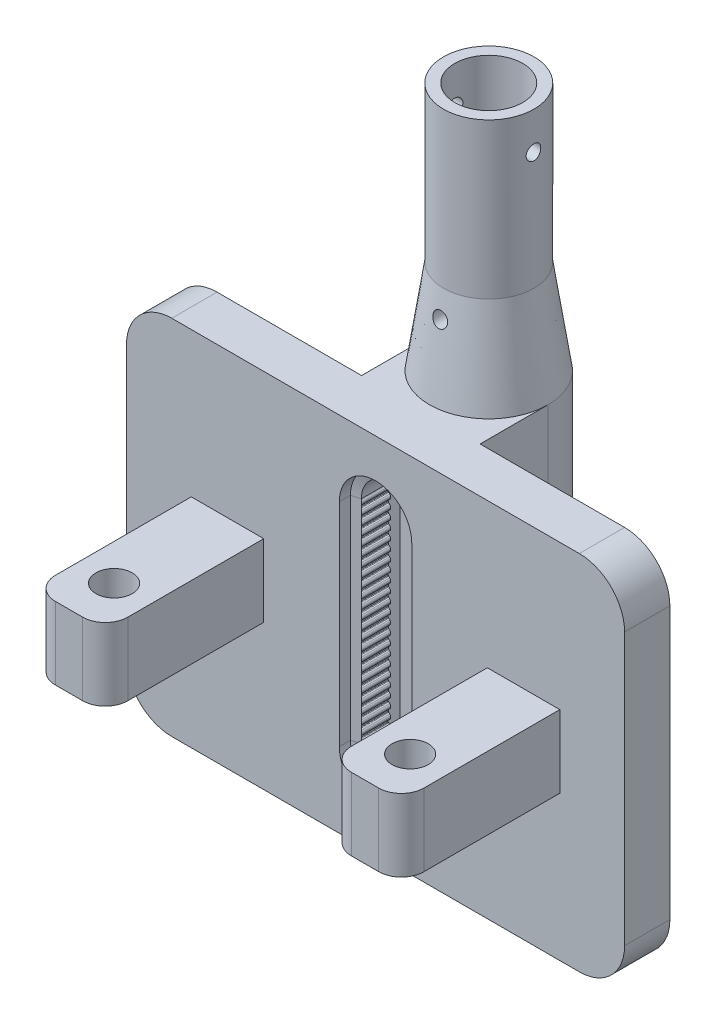
SolidWorks part; units mm, degrees
ref_plane "Piano frontale" through (0, 0, 0) normal (0, 0, 1) x (1, 0, 0)
ref_plane "Piano superiore" through (0, 0, 0) normal (0, 1, 0) x (1, 0, 0)
ref_plane "Piano destro" through (0, 0, 0) normal (1, 0, 0) x (0, 0, -1)
sketch "Schizzo1" plane through (0, 0, 0) normal (0, 0, 1) x (1, 0, 0)
  line L1 (-55, 40) -> (55, 40)
  line L2 (-55, 40) -> (-55, -40)
  line L3 (-55, -40) -> (55, -40)
  line L4 (55, 40) -> (55, -40)
  line L5 (-55, 40) -> (55, -40) construction
  line L6 (-55, -40) -> (55, 40) construction
  point P0 (0, 0)
  dimension "D1" = 80
  dimension "D2" = 110
extrude "Estrusione-Estrusione1" add sketch "Schizzo1" along normal blind 10
fillet "Raccordo1" radius 10 4 edges at (-55, -40, 5) (55, -40, 5) (55, 40, 5) (-55, 40, 5)
sketch "Schizzo2" plane through (0, 0, 10) normal (0, 0, 1) x (1, 0, 0)
  line L1 (-6.11, 27.5) -> (6.11, 27.5)
  line L2 (-6.11, 27.5) -> (-6.11, -27.5)
  line L3 (-6.11, -27.5) -> (6.11, -27.5)
  line L4 (6.11, 27.5) -> (6.11, -27.5)
  line L5 (-6.11, 27.5) -> (6.11, -27.5) construction
  line L6 (-6.11, -27.5) -> (6.11, 27.5) construction
  point P0 (0, 0)
  dimension "D1" = 55
  dimension "D2" = 12.22
extrude "Estrusione-Estrusione2" add sketch "Schizzo2" against normal blind 5 contours L1 L4 L3 L2
sketch "Schizzo6" plane through (0, 0, 10) normal (0, 0, 1) x (1, 0, 0)
  line L0 (0, 0) -> (49.9303, 0) construction
  line L2 (-6.11, 21.3859) -> (-6.11, -21.3859)
  line L4 (6.11, 21.3859) -> (6.11, -21.3859)
  line L5 (-6.11, 27.5) -> (6.11, -27.5) construction
  line L6 (-6.11, -27.5) -> (6.11, 27.5) construction
  arc A1 (6.11, -21.3859) -> (-6.11, -21.3859) centre (0, -21.3859) cw
  arc A2 (6.11, 21.3859) -> (-6.11, 21.3859) centre (0, 21.3859) ccw
  point P0 (0, 0)
  dimension "D1" = 12.22
  dimension "D2" = 55
extrude "Taglio-Estrusione6" cut sketch "Schizzo6" against normal blind 20
sketch "Schizzo9" plane through (0, 0, 0) normal (0, 0, -1) x (-1, 0, 0)
  line L0 (0, 0) -> (-26.4048, 0) construction
  line L1 (6.11, 23.4312) -> (6.11, -23.4312)
  line L2 (-6.11, 23.4312) -> (-6.11, -23.4312)
  arc A4 (6.11, 23.4312) -> (-6.11, 23.4312) centre (0, 23.4312) ccw
  arc A5 (-6.11, -23.4312) -> (6.11, -23.4312) centre (0, -23.4312) ccw
  point P0 (0, 0)
extrude "Taglio-Estrusione8" cut sketch "Schizzo9" against normal blind 53 contours A5 L1 A4 L2
ref_plane "Piano1" through (0, 95, 0) normal (0, 1, 0) x (1, 0, 0)
sketch "Schizzo14" plane through (0, 95, 0) normal (0, 1, 0) x (1, 0, 0)
  circle A1 centre (0, 15) radius 10
  dimension "D2" = 20
extrude "Estrusione-Estrusione5" add sketch "Schizzo14" against normal blind 135 separate body
ref_plane "Piano2" through (0, 0, 5) normal (0, 0, 1) x (1, 0, 0)
ref_plane "Piano3" through (0, -40, 0) normal (0, 1, 0) x (1, 0, 0)
sketch "Schizzo20" plane through (0, -40, 0) normal (0, 1, 0) x (1, 0, 0)
  line L0 (-13.0862, 15) -> (-13.0862, 0)
  line L1 (-45, 0) -> (45, 0) construction
  line L2 (-13.0862, 0) -> (13.0862, 0)
  line L3 (13.0862, 0) -> (13.0862, 15)
  arc A0 (13.0862, 15) -> (-13.0862, 15) centre (0, 15) ccw
chamfer "Smusso1" distance 2 angle 15 4 edges at (-6.11, 0, 0) (0, 29.5412, 0) (6.11, 0, 0) (0, -29.5412, 0) first distance on face at (0, 0, 0)
ref_plane "Piano4" through (0, 0, 7) normal (0, 0, 1) x (1, 0, 0)
sketch "Schizzo22" plane through (0, 0, 7) normal (0, 0, 1) x (1, 0, 0)
  line L0 (0, 0) -> (47.566, 0) construction
  line L1 (-8, 23.4312) -> (-8, -23.4312)
  line L2 (8, 23.4312) -> (8, -23.4312)
  arc A0 (8, 23.4312) -> (-8, 23.4312) centre (0, 23.4312) ccw
  arc A1 (8, -23.4312) -> (-8, -23.4312) centre (0, -23.4312) cw
extrude "Taglio-Estrusione12" cut sketch "Schizzo22" along normal blind 80 contours A0 L1 A1 L2
chamfer "Smusso2" distance 2 angle 15 4 edges at (0, -31.4312, 7) (-8, 0, 7) (0, 31.4312, 7) (8, 0, 7) first distance on face at (0, 0, 7)
extrude "Estrusione-Estrusione9" add sketch "Schizzo20" along normal blind 8 contours L0 L2 L3 A0
sketch "Schizzo23" plane through (0, -32, 0) normal (0, 1, 0) x (1, 0, 0)
  line L0 (-13.0862, 15) -> (-13.0862, 0)
  line L1 (-13.0862, 0) -> (-8.5862, 0)
  line L2 (-13.0862, 0) -> (13.0862, 0) construction
  line L3 (-8.5862, 0) -> (-6.5862, 2)
  line L4 (-6.5862, 2) -> (6.5862, 2)
  line L5 (6.5862, 2) -> (8.5862, 0)
  line L6 (-13.0862, 0) -> (13.0862, 0) construction
  line L7 (8.5862, 0) -> (13.0862, 0)
  line L8 (13.0862, 0) -> (13.0862, 15)
  arc A0 (13.0862, 15) -> (-13.0862, 15) centre (0, 15) ccw
  dimension "D1" = 4.5
  dimension "D2" = 45
  dimension "D3" = 4.5
  dimension "D4" = 2
extrude "Estrusione-Estrusione10" add sketch "Schizzo23" along normal blind 64
sketch "Schizzo24" plane through (0, 32, 0) normal (0, 1, 0) x (1, 0, 0)
  line L0 (-13.0862, 15) -> (-13.0862, 0)
  line L1 (-13.0862, 0) -> (13.0862, 0)
  line L2 (13.0862, 0) -> (13.0862, 15)
  arc A0 (13.0862, 15) -> (-13.0862, 15) centre (0, 15) ccw
extrude "Estrusione-Estrusione11" add sketch "Schizzo24" along normal blind 8
sketch "Schizzo25" plane through (0, 0, 0) normal (1, 0, 0) x (0, 0, -1)
  line L0 (15, 40) -> (15, 81.458) construction
  line L1 (15, 40) -> (28.0862, 40)
  line L2 (28.0862, 40) -> (25, 60.729)
  line L3 (25, 40) -> (25, 95) construction
  line L4 (25, 60.729) -> (15, 60.729)
  line L5 (15, 60.729) -> (15, 40)
revolve "Rivoluzione6" add sketch "Schizzo25" angle 360 about L0
sketch "Schizzo26" plane through (0, 0, 7) normal (0, 0, 1) x (1, 0, 0)
  line L0 (1.3785, -23.4315) -> (-1.3779, -23.431)
  line L1 (-6.8597, 21.1652) -> (-6.8597, 21.6893)
  line L2 (-6.8571, 15.416) -> (-6.8578, 15.1539)
  line L3 (-6.8575, 23.4312) -> (-6.8581, 23.1691)
  line L4 (-6.8571, 7.4009) -> (-6.8578, 7.1388)
  line L5 (-6.1096, 8.4039) -> (-6.1096, 8.4032) construction
  line L6 (1.3785, 23.4309) -> (-6.8575, 23.4312)
  line L7 (-6.8574, 19.4235) -> (-6.858, 19.6856)
  line L8 (-6.1096, 22.4287) -> (-6.1096, 22.4291) construction
  line L9 (-6.8571, -8.6292) -> (-6.8578, -8.8913)
  line L10 (-6.8574, 11.4084) -> (-6.858, 11.6705)
  line L11 (-6.1096, 22.4291) -> (-6.1096, 22.4287)
  line L12 (-6.1096, 22.4287) -> (-6.1096, 22.4291) construction
  line L13 (6.1099, -9.6321) -> (6.1099, -9.6314) construction
  line L14 (-6.8597, 13.1501) -> (-6.8597, 13.6743)
  line L15 (-6.8571, 15.416) -> (-6.8578, 15.6781)
  line L16 (-6.8597, 17.6818) -> (-6.8597, 17.1576)
  line L17 (-6.8574, 19.4235) -> (-6.858, 19.1614)
  line L18 (-6.1096, 8.4032) -> (-6.1096, 8.4039)
  line L19 (-6.8574, 11.4084) -> (-6.858, 11.1463)
  line L20 (-6.8571, 7.4009) -> (-6.8578, 7.663)
  line L21 (-6.8597, 9.6668) -> (-6.8597, 9.1426)
  line L22 (-6.1096, -7.6262) -> (-6.1096, -7.6269) construction
  line L23 (-6.1096, -6.6252) -> (-5.9547, -6.6252) construction
  line L24 (-6.1096, 6.3983) -> (-6.1096, 6.399) construction
  line L25 (-6.8597, 5.1351) -> (-6.8597, 5.6593)
  line L26 (-6.8574, 3.3934) -> (-6.858, 3.6555)
  line L27 (-6.1096, 6.399) -> (-6.1096, 6.3983)
  line L28 (-6.8574, -4.6217) -> (-6.858, -4.3596)
  line L29 (-6.8597, -2.88) -> (-6.8597, -2.3558)
  line L30 (-6.8571, -0.6141) -> (-6.8578, -0.8762)
  line L31 (-6.8597, 1.6517) -> (-6.8597, 1.1275)
  line L32 (-6.1096, -7.6269) -> (-6.1096, -7.6262)
  line L33 (-6.8574, 3.3934) -> (-6.858, 3.1313)
  line L34 (-6.8574, -4.6217) -> (-6.858, -4.8838)
  line L35 (-6.8571, -8.6292) -> (-6.8578, -8.3671)
  line L36 (-6.8571, -0.6141) -> (-6.8578, -0.352)
  line L37 (-6.8597, -6.3633) -> (-6.8597, -6.8875)
  line L38 (-6.1096, -10.6328) -> (-5.9547, -10.6328) construction
  line L39 (-6.1096, -9.6318) -> (-6.1096, -9.6311) construction
  line L40 (-6.8597, -10.895) -> (-6.8597, -10.3708)
  line L41 (-6.8571, -16.6442) -> (-6.8578, -16.9063)
  line L42 (-6.8574, -12.6367) -> (-6.858, -12.3746)
  line L43 (-6.8574, -20.6518) -> (-6.858, -20.3897)
  line L44 (-6.1096, -9.6311) -> (-6.1096, -9.6318)
  line L45 (-6.8597, -18.9101) -> (-6.8597, -18.3859)
  line L46 (-6.8571, -16.6442) -> (-6.8578, -16.3821)
  line L47 (-6.8597, -14.3784) -> (-6.8597, -14.9026)
  line L48 (-6.8574, -12.6367) -> (-6.858, -12.8988)
  line L50 (6.1099, -10.6331) -> (5.955, -10.6331) construction
  line L52 (6.1099, 6.398) -> (6.1099, 6.3987) construction
  line L53 (-6.8597, -22.3934) -> (-6.8597, -22.9176)
  line L54 (-6.8574, -20.6518) -> (-6.858, -20.9138)
  line L55 (-6.1578, -23.431) -> (-1.3779, -23.431)
  line L57 (6.1099, -6.6255) -> (5.955, -6.6255) construction
  line L58 (6.1099, -7.6265) -> (6.1099, -7.6272) construction
  line L59 (6.1099, 22.4281) -> (6.1099, 22.4288) construction
  line L60 (6.1099, 22.4281) -> (6.1099, 22.4288) construction
  line L61 (6.1099, 8.4036) -> (6.1099, 8.4029) construction
  line L62 (6.1581, -23.4315) -> (1.3785, -23.4315)
  line L63 (6.8577, -20.6522) -> (6.8583, -20.9143)
  line L64 (6.86, -22.3939) -> (6.86, -22.9181)
  line L65 (1.3785, 23.4309) -> (6.8581, 23.4309)
  line L66 (6.8577, -12.6372) -> (6.8583, -12.8993)
  line L67 (6.86, -14.3788) -> (6.86, -14.903)
  line L68 (6.8574, -16.6447) -> (6.8581, -16.3826)
  line L69 (6.86, -18.9106) -> (6.86, -18.3864)
  line L70 (6.1099, -9.6314) -> (6.1099, -9.6321)
  line L71 (6.8577, -20.6522) -> (6.8583, -20.3901)
  line L72 (6.8577, -12.6372) -> (6.8583, -12.3751)
  line L73 (6.8574, -16.6447) -> (6.8581, -16.9068)
  line L74 (6.86, -10.8955) -> (6.86, -10.3713)
  line L75 (6.86, -6.3638) -> (6.86, -6.888)
  line L76 (6.8574, -0.6146) -> (6.8581, -0.3525)
  line L77 (6.8574, -8.6296) -> (6.8581, -8.3675)
  line L78 (6.8577, -4.6221) -> (6.8583, -4.8842)
  line L79 (6.8577, 3.3929) -> (6.8583, 3.1308)
  line L80 (6.1099, -7.6272) -> (6.1099, -7.6265)
  line L81 (6.86, 1.6513) -> (6.86, 1.1271)
  line L82 (6.8574, -0.6146) -> (6.8581, -0.8767)
  line L83 (6.86, -2.8805) -> (6.86, -2.3563)
  line L84 (6.8577, -4.6221) -> (6.8583, -4.36)
  line L85 (6.1099, 6.3987) -> (6.1099, 6.398)
  line L86 (6.8577, 3.3929) -> (6.8583, 3.655)
  line L87 (6.86, 5.1346) -> (6.86, 5.6588)
  line L88 (6.86, 9.6663) -> (6.86, 9.1421)
  line L89 (6.8574, 7.4005) -> (6.8581, 7.6625)
  line L90 (6.8577, 11.408) -> (6.8583, 11.1459)
  line L91 (6.1099, 8.4029) -> (6.1099, 8.4036)
  line L92 (6.8577, 19.423) -> (6.8583, 19.1609)
  line L93 (6.86, 17.6814) -> (6.86, 17.1572)
  line L94 (6.8574, 15.4155) -> (6.8581, 15.6776)
  line L95 (6.86, 13.1496) -> (6.86, 13.6738)
  line L96 (6.1099, 22.4288) -> (6.1099, 22.4281)
  line L97 (6.8577, 11.408) -> (6.8583, 11.6701)
  line L98 (6.8574, -8.6296) -> (6.8581, -8.8917)
  line L99 (6.8577, 19.423) -> (6.8583, 19.6851)
  line L101 (6.8574, 7.4005) -> (6.8581, 7.1384)
  line L102 (6.8581, 23.4309) -> (6.8587, 23.1688)
  line L103 (6.8574, 15.4155) -> (6.8581, 15.1534)
  line L104 (6.86, 21.1647) -> (6.86, 21.6889)
  arc A0 (-6.4213, 21.93) -> (-6.421, 22.9276) centre (-6.6647, 22.4289) ccw
  arc A1 (-6.7298, 21.8372) -> (-6.4213, 21.93) centre (-6.8596, 22.8284) ccw
  arc A2 (-6.7298, 21.8372) -> (-6.8597, 21.6893) centre (-6.7105, 21.6893) ccw
  arc A3 (-6.7287, 23.0208) -> (-6.8581, 23.1691) centre (-6.7089, 23.1687) cw
  arc A4 (-6.7287, 23.0208) -> (-6.421, 22.9276) centre (-6.8609, 22.0301) cw
  arc A5 (-6.7299, 21.0172) -> (-6.8597, 21.1652) centre (-6.7105, 21.1651) cw
  arc A6 (-6.7299, 21.0172) -> (-6.4214, 20.9244) centre (-6.8598, 20.0261) cw
  arc A7 (-6.7286, 19.8338) -> (-6.858, 19.6856) centre (-6.7088, 19.6859) ccw
  arc A8 (-6.7286, 19.8338) -> (-6.4202, 19.9273) centre (-6.8607, 20.8246) ccw
  arc A9 (-6.4214, 20.9244) -> (-6.4202, 19.9273) centre (-6.6648, 20.4256) cw
  arc A10 (-6.7298, 17.0097) -> (-6.8597, 17.1576) centre (-6.7105, 17.1576) cw
  arc A11 (-6.7284, 15.8263) -> (-6.8578, 15.6781) centre (-6.7086, 15.6784) ccw
  arc A12 (-6.7284, 15.8263) -> (-6.42, 15.9198) centre (-6.8606, 16.8171) ccw
  arc A13 (-6.4213, 16.917) -> (-6.42, 15.9198) centre (-6.6647, 16.4181) cw
  arc A14 (-6.7298, 17.0097) -> (-6.4213, 16.917) centre (-6.8596, 16.0186) cw
  arc A15 (-6.7299, 17.8297) -> (-6.8597, 17.6818) centre (-6.7105, 17.6818) ccw
  arc A16 (-6.7299, 17.8297) -> (-6.4214, 17.9225) centre (-6.8598, 18.8208) ccw
  arc A17 (-6.4214, 17.9225) -> (-6.4202, 18.9197) centre (-6.6648, 18.4214) ccw
  arc A18 (-6.7286, 19.0132) -> (-6.4202, 18.9197) centre (-6.8607, 18.0224) cw
  arc A19 (-6.7286, 19.0132) -> (-6.858, 19.1614) centre (-6.7088, 19.161) cw
  arc A20 (-6.7286, 11.8187) -> (-6.858, 11.6705) centre (-6.7088, 11.6709) ccw
  arc A21 (-6.7286, 11.8187) -> (-6.4202, 11.9122) centre (-6.8607, 12.8095) ccw
  arc A22 (-6.4214, 12.9094) -> (-6.4202, 11.9122) centre (-6.6648, 12.4105) cw
  arc A23 (-6.7299, 13.0022) -> (-6.4214, 12.9094) centre (-6.8598, 12.0111) cw
  arc A24 (-6.7299, 13.0022) -> (-6.8597, 13.1501) centre (-6.7105, 13.1501) cw
  arc A25 (-6.7298, 13.8222) -> (-6.4213, 13.915) centre (-6.8596, 14.8133) ccw
  arc A26 (-6.4213, 13.915) -> (-6.42, 14.9121) centre (-6.6647, 14.4138) ccw
  arc A27 (-6.7284, 15.0056) -> (-6.42, 14.9121) centre (-6.8606, 14.0149) cw
  arc A28 (-6.7284, 15.0056) -> (-6.8578, 15.1539) centre (-6.7086, 15.1535) cw
  arc A29 (-6.7298, 13.8222) -> (-6.8597, 13.6743) centre (-6.7105, 13.6743) ccw
  arc A30 (-6.4214, 9.9075) -> (-6.4202, 10.9046) centre (-6.6648, 10.4063) ccw
  arc A31 (-6.7286, 10.9981) -> (-6.4202, 10.9046) centre (-6.8607, 10.0073) cw
  arc A32 (-6.7286, 10.9981) -> (-6.858, 11.1463) centre (-6.7088, 11.146) cw
  arc A33 (-6.7299, 9.8147) -> (-6.4214, 9.9075) centre (-6.8598, 10.8058) ccw
  arc A34 (-6.7299, 9.8147) -> (-6.8597, 9.6668) centre (-6.7105, 9.6668) ccw
  arc A35 (-6.7284, 7.8112) -> (-6.42, 7.9048) centre (-6.8606, 8.802) ccw
  arc A36 (-6.7284, 7.8112) -> (-6.8578, 7.663) centre (-6.7086, 7.6634) ccw
  arc A37 (-6.7298, 8.9947) -> (-6.8597, 9.1426) centre (-6.7105, 9.1426) cw
  arc A38 (-6.7298, 8.9947) -> (-6.4213, 8.9019) centre (-6.8596, 8.0036) cw
  arc A39 (-6.4213, 8.9019) -> (-6.42, 7.9048) centre (-6.6647, 8.403) cw
  arc A40 (-6.4213, 5.8999) -> (-6.42, 6.8971) centre (-6.6647, 6.3988) ccw
  arc A41 (-6.7298, 5.8072) -> (-6.4213, 5.8999) centre (-6.8596, 6.7983) ccw
  arc A42 (-6.7298, 5.8072) -> (-6.8597, 5.6593) centre (-6.7105, 5.6592) ccw
  arc A43 (-6.7284, 6.9906) -> (-6.8578, 7.1388) centre (-6.7086, 7.1385) cw
  arc A44 (-6.7284, 6.9906) -> (-6.42, 6.8971) centre (-6.8606, 5.9998) cw
  arc A45 (-6.7299, 4.9871) -> (-6.8597, 5.1351) centre (-6.7105, 5.135) cw
  arc A46 (-6.7299, 4.9871) -> (-6.4214, 4.8943) centre (-6.8598, 3.996) cw
  arc A47 (-6.7286, 3.8037) -> (-6.858, 3.6555) centre (-6.7088, 3.6558) ccw
  arc A48 (-6.7286, 3.8037) -> (-6.4202, 3.8972) centre (-6.8607, 4.7945) ccw
  arc A49 (-6.4214, 4.8943) -> (-6.4202, 3.8972) centre (-6.6648, 4.3955) cw
  arc A50 (-6.7298, 0.9796) -> (-6.8597, 1.1275) centre (-6.7105, 1.1275) cw
  arc A51 (-6.7284, -0.2038) -> (-6.8578, -0.352) centre (-6.7086, -0.3517) ccw
  arc A52 (-6.7284, -0.2038) -> (-6.42, -0.1103) centre (-6.8606, 0.787) ccw
  arc A53 (-6.4213, 0.8869) -> (-6.42, -0.1103) centre (-6.6647, 0.388) cw
  arc A54 (-6.7298, 0.9796) -> (-6.4213, 0.8869) centre (-6.8596, -0.0115) cw
  arc A55 (-6.7299, 1.7996) -> (-6.8597, 1.6517) centre (-6.7105, 1.6517) ccw
  arc A56 (-6.7299, 1.7996) -> (-6.4214, 1.8924) centre (-6.8598, 2.7907) ccw
  arc A57 (-6.4214, 1.8924) -> (-6.4202, 2.8896) centre (-6.6648, 2.3913) ccw
  arc A58 (-6.7286, 2.9831) -> (-6.4202, 2.8896) centre (-6.8607, 1.9923) cw
  arc A59 (-6.7286, 2.9831) -> (-6.858, 3.1313) centre (-6.7088, 3.1309) cw
  arc A60 (-6.7286, -4.2113) -> (-6.858, -4.3596) centre (-6.7088, -4.3592) ccw
  arc A61 (-6.7286, -4.2113) -> (-6.4202, -4.1179) centre (-6.8607, -3.2206) ccw
  arc A62 (-6.4214, -3.1207) -> (-6.4202, -4.1179) centre (-6.6648, -3.6196) cw
  arc A63 (-6.7299, -3.0279) -> (-6.4214, -3.1207) centre (-6.8598, -4.019) cw
  arc A64 (-6.7299, -3.0279) -> (-6.8597, -2.88) centre (-6.7105, -2.88) cw
  arc A65 (-6.7298, -2.2079) -> (-6.4213, -2.1151) centre (-6.8596, -1.2168) ccw
  arc A66 (-6.4213, -2.1151) -> (-6.42, -1.118) centre (-6.6647, -1.6163) ccw
  arc A67 (-6.7284, -1.0245) -> (-6.42, -1.118) centre (-6.8606, -2.0152) cw
  arc A68 (-6.7284, -1.0245) -> (-6.8578, -0.8762) centre (-6.7086, -0.8766) cw
  arc A69 (-6.7298, -2.2079) -> (-6.8597, -2.3558) centre (-6.7105, -2.3558) ccw
  arc A70 (-6.4214, -6.1226) -> (-6.4202, -5.1255) centre (-6.6648, -5.6238) ccw
  arc A71 (-6.7286, -5.032) -> (-6.4202, -5.1255) centre (-6.8607, -6.0228) cw
  arc A72 (-6.7286, -5.032) -> (-6.858, -4.8838) centre (-6.7088, -4.8841) cw
  arc A73 (-6.7299, -6.2154) -> (-6.4214, -6.1226) centre (-6.8598, -5.2243) ccw
  arc A74 (-6.7299, -6.2154) -> (-6.8597, -6.3633) centre (-6.7105, -6.3633) ccw
  arc A75 (-6.7284, -8.2189) -> (-6.42, -8.1253) centre (-6.8606, -7.2281) ccw
  arc A76 (-6.7284, -8.2189) -> (-6.8578, -8.3671) centre (-6.7086, -8.3667) ccw
  arc A77 (-6.7298, -7.0354) -> (-6.8597, -6.8875) centre (-6.7105, -6.8875) cw
  arc A78 (-6.7298, -7.0354) -> (-6.4213, -7.1282) centre (-6.8596, -8.0265) cw
  arc A79 (-6.4213, -7.1282) -> (-6.42, -8.1253) centre (-6.6647, -7.6271) cw
  arc A80 (-6.4213, -10.1302) -> (-6.42, -9.133) centre (-6.6647, -9.6313) ccw
  arc A81 (-6.7298, -10.2229) -> (-6.4213, -10.1302) centre (-6.8596, -9.2318) ccw
  arc A82 (-6.7298, -10.2229) -> (-6.8597, -10.3708) centre (-6.7105, -10.3709) ccw
  arc A83 (-6.7284, -9.0395) -> (-6.8578, -8.8913) centre (-6.7086, -8.8916) cw
  arc A84 (-6.7284, -9.0395) -> (-6.42, -9.133) centre (-6.8606, -10.0303) cw
  arc A85 (-6.7299, -11.043) -> (-6.8597, -10.895) centre (-6.7105, -10.895) cw
  arc A86 (-6.7299, -11.043) -> (-6.4214, -11.1358) centre (-6.8598, -12.034) cw
  arc A87 (-6.7286, -12.2264) -> (-6.858, -12.3746) centre (-6.7088, -12.3743) ccw
  arc A88 (-6.7286, -12.2264) -> (-6.4202, -12.1329) centre (-6.8607, -11.2356) ccw
  arc A89 (-6.4214, -11.1358) -> (-6.4202, -12.1329) centre (-6.6648, -11.6346) cw
  arc A90 (-6.7298, -15.0505) -> (-6.8597, -14.9026) centre (-6.7105, -14.9026) cw
  arc A91 (-6.7284, -16.2339) -> (-6.8578, -16.3821) centre (-6.7086, -16.3818) ccw
  arc A92 (-6.7284, -16.2339) -> (-6.42, -16.1404) centre (-6.8606, -15.2431) ccw
  arc A93 (-6.4213, -15.1432) -> (-6.42, -16.1404) centre (-6.6647, -15.6421) cw
  arc A94 (-6.7298, -15.0505) -> (-6.4213, -15.1432) centre (-6.8596, -16.0416) cw
  arc A95 (-6.7299, -14.2305) -> (-6.8597, -14.3784) centre (-6.7105, -14.3784) ccw
  arc A96 (-6.7299, -14.2305) -> (-6.4214, -14.1377) centre (-6.8598, -13.2394) ccw
  arc A97 (-6.4214, -14.1377) -> (-6.4202, -13.1405) centre (-6.6648, -13.6388) ccw
  arc A98 (-6.7286, -13.047) -> (-6.4202, -13.1405) centre (-6.8607, -14.0378) cw
  arc A99 (-6.7286, -13.047) -> (-6.858, -12.8988) centre (-6.7088, -12.8991) cw
  arc A100 (-6.7286, -20.2414) -> (-6.858, -20.3897) centre (-6.7088, -20.3893) ccw
  arc A101 (-6.7286, -20.2414) -> (-6.4202, -20.1479) centre (-6.8607, -19.2506) ccw
  arc A102 (-6.4214, -19.1508) -> (-6.4202, -20.1479) centre (-6.6648, -19.6496) cw
  arc A103 (-6.7299, -19.058) -> (-6.4214, -19.1508) centre (-6.8598, -20.0491) cw
  arc A104 (-6.7299, -19.058) -> (-6.8597, -18.9101) centre (-6.7105, -18.9101) cw
  arc A105 (-6.7298, -18.238) -> (-6.4213, -18.1452) centre (-6.8596, -17.2469) ccw
  arc A106 (-6.4213, -18.1452) -> (-6.42, -17.1481) centre (-6.6647, -17.6464) ccw
  arc A107 (-6.7284, -17.0545) -> (-6.42, -17.1481) centre (-6.8606, -18.0453) cw
  arc A108 (-6.7284, -17.0545) -> (-6.8578, -16.9063) centre (-6.7086, -16.9067) cw
  arc A109 (-6.7298, -18.238) -> (-6.8597, -18.3859) centre (-6.7105, -18.3859) ccw
  arc A110 (6.8581, 23.4309) -> (6.8511, 23.1213) centre (0.0006, 23.4309) cw construction
  arc A111 (-6.8575, 23.4312) -> (-6.8505, 23.1216) centre (0.0006, 23.4309) ccw construction
  arc A112 (6.7289, -21.0625) -> (6.8583, -20.9143) centre (6.7091, -20.9147) ccw
  arc A113 (-6.4213, -23.1583) -> (-6.1578, -23.431) centre (-6.6647, -23.6571) cw
  arc A114 (-6.7298, -23.0655) -> (-6.4213, -23.1583) centre (-6.8596, -24.0566) cw
  arc A115 (-6.7298, -23.0655) -> (-6.8597, -22.9176) centre (-6.7105, -22.9176) cw
  arc A116 (-6.7299, -22.2455) -> (-6.8597, -22.3934) centre (-6.7105, -22.3934) ccw
  arc A117 (-6.7299, -22.2455) -> (-6.4214, -22.1527) centre (-6.8598, -21.2544) ccw
  arc A118 (-6.4214, -22.1527) -> (-6.4202, -21.1556) centre (-6.6648, -21.6539) ccw
  arc A119 (-6.7286, -21.0621) -> (-6.4202, -21.1556) centre (-6.8607, -22.0529) cw
  arc A120 (-6.7286, -21.0621) -> (-6.858, -20.9138) centre (-6.7088, -20.9142) cw
  arc A121 (6.7289, -21.0625) -> (6.4205, -21.156) centre (6.861, -22.0533) ccw
  arc A122 (6.4217, -22.1532) -> (6.4205, -21.156) centre (6.6651, -21.6543) cw
  arc A123 (6.7302, -22.246) -> (6.4217, -22.1532) centre (6.8601, -21.2549) cw
  arc A124 (6.7302, -22.246) -> (6.86, -22.3939) centre (6.7108, -22.3939) cw
  arc A125 (6.7301, -23.066) -> (6.86, -22.9181) centre (6.7108, -22.9181) ccw
  arc A126 (6.7301, -23.066) -> (6.4216, -23.1587) centre (6.8599, -24.0571) ccw
  arc A127 (6.4216, -23.1587) -> (6.1581, -23.4315) centre (6.665, -23.6576) ccw
  arc A128 (6.7301, -18.2385) -> (6.86, -18.3864) centre (6.7108, -18.3864) cw
  arc A129 (6.7287, -17.055) -> (6.8581, -16.9068) centre (6.7089, -16.9072) ccw
  arc A130 (6.7287, -17.055) -> (6.4203, -17.1486) centre (6.8609, -18.0458) ccw
  arc A131 (6.4216, -18.1457) -> (6.4203, -17.1486) centre (6.665, -17.6468) cw
  arc A132 (6.7301, -18.2385) -> (6.4216, -18.1457) centre (6.8599, -17.2473) cw
  arc A133 (6.7302, -19.0585) -> (6.86, -18.9106) centre (6.7108, -18.9106) ccw
  arc A134 (6.7302, -19.0585) -> (6.4217, -19.1513) centre (6.8601, -20.0496) ccw
  arc A135 (6.4217, -19.1513) -> (6.4205, -20.1484) centre (6.6651, -19.6501) ccw
  arc A136 (6.7289, -20.2419) -> (6.4205, -20.1484) centre (6.861, -19.2511) cw
  arc A137 (6.7289, -20.2419) -> (6.8583, -20.3901) centre (6.7091, -20.3898) cw
  arc A138 (6.7289, -13.0475) -> (6.8583, -12.8993) centre (6.7091, -12.8996) ccw
  arc A139 (6.7289, -13.0475) -> (6.4205, -13.141) centre (6.861, -14.0383) ccw
  arc A140 (6.4217, -14.1381) -> (6.4205, -13.141) centre (6.6651, -13.6393) cw
  arc A141 (6.7302, -14.2309) -> (6.4217, -14.1381) centre (6.8601, -13.2398) cw
  arc A142 (6.7302, -14.2309) -> (6.86, -14.3788) centre (6.7108, -14.3788) cw
  arc A143 (6.7301, -15.0509) -> (6.4216, -15.1437) centre (6.8599, -16.042) ccw
  arc A144 (6.4216, -15.1437) -> (6.4203, -16.1408) centre (6.665, -15.6426) ccw
  arc A145 (6.7287, -16.2344) -> (6.4203, -16.1408) centre (6.8609, -15.2436) cw
  arc A146 (6.7287, -16.2344) -> (6.8581, -16.3826) centre (6.7089, -16.3822) cw
  arc A147 (6.7301, -15.0509) -> (6.86, -14.903) centre (6.7108, -14.903) ccw
  arc A148 (6.4217, -11.1362) -> (6.4205, -12.1334) centre (6.6651, -11.6351) ccw
  arc A149 (6.7289, -12.2269) -> (6.4205, -12.1334) centre (6.861, -11.2361) cw
  arc A150 (6.7289, -12.2269) -> (6.8583, -12.3751) centre (6.7091, -12.3747) cw
  arc A151 (6.7302, -11.0434) -> (6.4217, -11.1362) centre (6.8601, -12.0345) ccw
  arc A152 (6.7302, -11.0434) -> (6.86, -10.8955) centre (6.7108, -10.8955) ccw
  arc A153 (6.7287, -9.04) -> (6.4203, -9.1335) centre (6.8609, -10.0307) ccw
  arc A154 (6.7287, -9.04) -> (6.8581, -8.8917) centre (6.7089, -8.8921) ccw
  arc A155 (6.7301, -10.2234) -> (6.86, -10.3713) centre (6.7108, -10.3713) cw
  arc A156 (6.7301, -10.2234) -> (6.4216, -10.1307) centre (6.8599, -9.2323) cw
  arc A157 (6.4216, -10.1307) -> (6.4203, -9.1335) centre (6.665, -9.6318) cw
  arc A158 (6.4216, -7.1286) -> (6.4203, -8.1258) centre (6.665, -7.6275) ccw
  arc A159 (6.7301, -7.0359) -> (6.4216, -7.1286) centre (6.8599, -8.027) ccw
  arc A160 (6.7301, -7.0359) -> (6.86, -6.888) centre (6.7108, -6.888) ccw
  arc A161 (6.7287, -8.2193) -> (6.8581, -8.3675) centre (6.7089, -8.3672) cw
  arc A162 (6.7287, -8.2193) -> (6.4203, -8.1258) centre (6.8609, -7.2285) cw
  arc A163 (6.7302, -6.2159) -> (6.86, -6.3638) centre (6.7108, -6.3638) cw
  arc A164 (6.7302, -6.2159) -> (6.4217, -6.1231) centre (6.8601, -5.2248) cw
  arc A165 (6.7289, -5.0324) -> (6.8583, -4.8842) centre (6.7091, -4.8846) ccw
  arc A166 (6.7289, -5.0324) -> (6.4205, -5.1259) centre (6.861, -6.0232) ccw
  arc A167 (6.4217, -6.1231) -> (6.4205, -5.1259) centre (6.6651, -5.6242) cw
  arc A168 (6.7301, -2.2084) -> (6.86, -2.3563) centre (6.7108, -2.3563) cw
  arc A169 (6.7287, -1.0249) -> (6.8581, -0.8767) centre (6.7089, -0.8771) ccw
  arc A170 (6.7287, -1.0249) -> (6.4203, -1.1185) centre (6.8609, -2.0157) ccw
  arc A171 (6.4216, -2.1156) -> (6.4203, -1.1185) centre (6.665, -1.6167) cw
  arc A172 (6.7301, -2.2084) -> (6.4216, -2.1156) centre (6.8599, -1.2172) cw
  arc A173 (6.7302, -3.0284) -> (6.86, -2.8805) centre (6.7108, -2.8805) ccw
  arc A174 (6.7302, -3.0284) -> (6.4217, -3.1212) centre (6.8601, -4.0195) ccw
  arc A175 (6.4217, -3.1212) -> (6.4205, -4.1183) centre (6.6651, -3.62) ccw
  arc A176 (6.7289, -4.2118) -> (6.4205, -4.1183) centre (6.861, -3.221) cw
  arc A177 (6.7289, -4.2118) -> (6.8583, -4.36) centre (6.7091, -4.3597) cw
  arc A178 (6.7289, 2.9826) -> (6.8583, 3.1308) centre (6.7091, 3.1305) ccw
  arc A179 (6.7289, 2.9826) -> (6.4205, 2.8891) centre (6.861, 1.9918) ccw
  arc A180 (6.4217, 1.892) -> (6.4205, 2.8891) centre (6.6651, 2.3908) cw
  arc A181 (6.7302, 1.7992) -> (6.4217, 1.892) centre (6.8601, 2.7903) cw
  arc A182 (6.7302, 1.7992) -> (6.86, 1.6513) centre (6.7108, 1.6513) cw
  arc A183 (6.7301, 0.9792) -> (6.4216, 0.8864) centre (6.8599, -0.0119) ccw
  arc A184 (6.4216, 0.8864) -> (6.4203, -0.1107) centre (6.665, 0.3875) ccw
  arc A185 (6.7287, -0.2043) -> (6.4203, -0.1107) centre (6.8609, 0.7865) cw
  arc A186 (6.7287, -0.2043) -> (6.8581, -0.3525) centre (6.7089, -0.3521) cw
  arc A187 (6.7301, 0.9792) -> (6.86, 1.1271) centre (6.7108, 1.1271) ccw
  arc A188 (6.4217, 4.8939) -> (6.4205, 3.8967) centre (6.6651, 4.395) ccw
  arc A189 (6.7289, 3.8032) -> (6.4205, 3.8967) centre (6.861, 4.794) cw
  arc A190 (6.7289, 3.8032) -> (6.8583, 3.655) centre (6.7091, 3.6554) cw
  arc A191 (6.7302, 4.9867) -> (6.4217, 4.8939) centre (6.8601, 3.9956) ccw
  arc A192 (6.7302, 4.9867) -> (6.86, 5.1346) centre (6.7108, 5.1346) ccw
  arc A193 (6.7287, 6.9901) -> (6.4203, 6.8966) centre (6.8609, 5.9993) ccw
  arc A194 (6.7287, 6.9901) -> (6.8581, 7.1384) centre (6.7089, 7.138) ccw
  arc A195 (6.7301, 5.8067) -> (6.86, 5.6588) centre (6.7108, 5.6588) cw
  arc A196 (6.7301, 5.8067) -> (6.4216, 5.8994) centre (6.8599, 6.7978) cw
  arc A197 (6.4216, 5.8994) -> (6.4203, 6.8966) centre (6.665, 6.3983) cw
  arc A198 (6.4216, 8.9015) -> (6.4203, 7.9043) centre (6.665, 8.4026) ccw
  arc A199 (6.7301, 8.9942) -> (6.4216, 8.9015) centre (6.8599, 8.0031) ccw
  arc A200 (6.7301, 8.9942) -> (6.86, 9.1421) centre (6.7108, 9.1421) ccw
  arc A201 (6.7287, 7.8108) -> (6.8581, 7.6625) centre (6.7089, 7.6629) cw
  arc A202 (6.7287, 7.8108) -> (6.4203, 7.9043) centre (6.8609, 8.8016) cw
  arc A203 (6.7302, 9.8142) -> (6.86, 9.6663) centre (6.7108, 9.6663) cw
  arc A204 (6.7302, 9.8142) -> (6.4217, 9.907) centre (6.8601, 10.8053) cw
  arc A205 (6.7289, 10.9977) -> (6.8583, 11.1459) centre (6.7091, 11.1455) ccw
  arc A206 (6.7289, 10.9977) -> (6.4205, 10.9042) centre (6.861, 10.0069) ccw
  arc A207 (6.4217, 9.907) -> (6.4205, 10.9042) centre (6.6651, 10.4059) cw
  arc A208 (6.7301, 13.8217) -> (6.86, 13.6738) centre (6.7108, 13.6738) cw
  arc A209 (6.7287, 15.0052) -> (6.8581, 15.1534) centre (6.7089, 15.153) ccw
  arc A210 (6.7287, 15.0052) -> (6.4203, 14.9116) centre (6.8609, 14.0144) ccw
  arc A211 (6.4216, 13.9145) -> (6.4203, 14.9116) centre (6.665, 14.4134) cw
  arc A212 (6.7301, 13.8217) -> (6.4216, 13.9145) centre (6.8599, 14.8128) cw
  arc A213 (6.7302, 13.0017) -> (6.86, 13.1496) centre (6.7108, 13.1496) ccw
  arc A214 (6.7302, 13.0017) -> (6.4217, 12.9089) centre (6.8601, 12.0106) ccw
  arc A215 (6.4217, 12.9089) -> (6.4205, 11.9118) centre (6.6651, 12.4101) ccw
  arc A216 (6.7289, 11.8183) -> (6.4205, 11.9118) centre (6.861, 12.8091) cw
  arc A217 (6.7289, 11.8183) -> (6.8583, 11.6701) centre (6.7091, 11.6704) cw
  arc A218 (6.7289, 19.0127) -> (6.8583, 19.1609) centre (6.7091, 19.1606) ccw
  arc A219 (6.7289, 19.0127) -> (6.4205, 18.9192) centre (6.861, 18.0219) ccw
  arc A220 (6.4217, 17.9221) -> (6.4205, 18.9192) centre (6.6651, 18.4209) cw
  arc A221 (6.7302, 17.8293) -> (6.4217, 17.9221) centre (6.8601, 18.8204) cw
  arc A222 (6.7302, 17.8293) -> (6.86, 17.6814) centre (6.7108, 17.6814) cw
  arc A223 (6.7301, 17.0093) -> (6.4216, 16.9165) centre (6.8599, 16.0182) ccw
  arc A224 (6.4216, 16.9165) -> (6.4203, 15.9194) centre (6.665, 16.4176) ccw
  arc A225 (6.7287, 15.8258) -> (6.4203, 15.9194) centre (6.8609, 16.8166) cw
  arc A226 (6.7287, 15.8258) -> (6.8581, 15.6776) centre (6.7089, 15.678) cw
  arc A227 (6.7301, 17.0093) -> (6.86, 17.1572) centre (6.7108, 17.1572) ccw
  arc A228 (6.4217, 20.924) -> (6.4205, 19.9268) centre (6.6651, 20.4251) ccw
  arc A229 (6.7289, 19.8333) -> (6.4205, 19.9268) centre (6.861, 20.8241) cw
  arc A230 (6.7289, 19.8333) -> (6.8583, 19.6851) centre (6.7091, 19.6855) cw
  arc A231 (6.7302, 21.0168) -> (6.4217, 20.924) centre (6.8601, 20.0257) ccw
  arc A232 (6.7302, 21.0168) -> (6.86, 21.1647) centre (6.7108, 21.1647) ccw
  arc A233 (6.7293, 23.0205) -> (6.421, 22.927) centre (6.8615, 22.0298) ccw
  arc A234 (6.7293, 23.0205) -> (6.8587, 23.1688) centre (6.7095, 23.1684) ccw
  arc A235 (6.7301, 21.8368) -> (6.86, 21.6889) centre (6.7108, 21.6889) cw
  arc A236 (6.7301, 21.8368) -> (6.4216, 21.9295) centre (6.8599, 22.8279) cw
  arc A237 (6.4216, 21.9295) -> (6.421, 22.927) centre (6.665, 22.4284) cw
  point P24 (-6.8597, 21.4273)
  point P109 (-6.8597, 9.4049)
  point P204 (-6.8597, 5.3973)
  point P205 (-6.8597, -6.6252)
  point P278 (-6.8597, -10.6328)
  point P587 (6.86, -10.6331)
  point P588 (6.86, -6.6255)
  point P589 (6.86, 5.397)
  point P590 (6.86, 9.4046)
  point P591 (6.86, 21.4268)
extrude "Taglio-Estrusione14" cut sketch "Schizzo26" against normal blind 8 contours L3 A3 A4 A0 A1 A2 L1 A5 A6 A9 A8 A7 L7 L17 A19 A18 A17 A16 A15 L16 A10 A14 A13 A12 A11 L15 L2 A28 A27 A26 A25 A29 L14 A24 A23 A22 A21 A20 L10 L19 A32 A31 A30 A33 A34 L21 A37 A38 A39 A35 A36 L20 L4 A43 A44 A40 A41 A42 L25 A45 A46 A49 A48 A47 L26 L33 A59 A58 A57 A56 A55 L31 A50 A54 A53 A52 A51 L36 L30 A68 A67 A66 A65 A69 L29 A64 A63 A62 A61 A60 L28 L34 A72 A71 A70 A73 A74 L37 A77 A78 A79 A75 A76 L35 L9 A83 A84 A80 A81 A82 L40 A85 A86 A89 A88 A87 L42 L48 A99 A98 A97 A96 A95 L47 A90 A94 A93 A92 A91 L46 L41 A108 A107 A106 A105 A109 L45 A104 A103 A102 A101 A100 L43 L54 A120 A119 A118 A117 A116 L53 A115 A114 A113 L55 L0 L62 A127 A126 A125 L64 A124 A123 A122 A121 A112 L63 L71 A137 A136 A135 A134 A133 L69 A128 A132 A131 A130 A129 L73 L68 A146 A145 A144 A143 A147 L67 A142 A141 A140 A139 A138 L66 L72 A150 A149 A148 A151 A152 L74 A155 A156 A157 A153 A154 L98 L77 A161 A162 A158 A159 A160 L75 A163 A164 A167 A166 A165 L78 L84 A177 A176 A175 A174 A173 L83 A168 A172 A171 A170 A169 L82 L76 A186 A185 A184 A183 A187 L81 A182 A181 A180 A179 A178 L79 L86 A190 A189 A188 A191 A192 L87 A195 A196 A197 A193 A194 L101 L89 A201 A202 A198 A199 A200 L88 A203 A204 A207 A206 A205 L90 L97 A217 A216 A215 A214 A213 L95 A208 A212 A211 A210 A209 L103 L94 A226 A225 A224 A223 A227 L93 A222 A221 A220 A219 A218 L92 L99 A230 A229 A228 A231 A232 L104 A235 A236 A237 A233 A234 L102 L65 L6
sketch "Schizzo32" plane through (0, 0, 10) normal (0, 0, 1) x (1, 0, 0)
  line L0 (0, 0) -> (-65.759, 0) construction
  line L1 (-55, 30) -> (-55, -30) construction
  line L2 (-24.69, 8) -> (-40.69, 8)
  line L3 (-24.69, 8) -> (-24.69, -8)
  line L4 (-24.69, -8) -> (-40.69, -8)
  line L5 (-40.69, 8) -> (-40.69, -8)
  line L6 (-24.69, 8) -> (-40.69, -8) construction
  line L7 (-24.69, -8) -> (-40.69, 8) construction
  point P3 (-32.69, 0)
  dimension "D1" = 16
  dimension "D2" = 16
  dimension "D3" = 22.31
extrude "Estrusione-Estrusione13" add sketch "Schizzo32" along normal blind 35 contours L5 L4 L3 L2
fillet "Raccordo7" radius 5 2 edges at (-24.69, 0, 45) (-40.69, 0, 45)
sketch "Schizzo33" plane through (0, 8, 0) normal (0, 1, 0) x (1, 0, 0)
  line L0 (-32.69, -45) -> (-32.69, -19.6568) construction
  line L1 (-29.69, -45) -> (-35.69, -45) construction
  circle A0 centre (-32.69, -35.05) radius 4
  dimension "D1" = 9.95
extrude "Taglio-Estrusione16" cut sketch "Schizzo33" against normal blind 35
mirror "Specchia1" about plane through (0, 0, 0) normal (1, 0, 0) of "Raccordo7", "Taglio-Estrusione16", "Estrusione-Estrusione13"
sketch "Schizzo35" plane through (0, 95, 0) normal (0, 1, 0) x (1, 0, 0)
  circle A0 centre (0, 15) radius 7.5
extrude "Taglio-Estrusione17" cut sketch "Schizzo35" against normal blind 47.44 contours A0
ref_plane "Piano6" through (0, 55, 0) normal (0, 1, 0) x (1, 0, 0)
sketch "Schizzo36" plane through (0, 0, 0) normal (0, 0, 1) x (1, 0, 0)
  line L1 (0, 95) -> (0, 14.6353) construction
  line L2 (10, 95) -> (-10, 95) construction
  circle A1 centre (0, 55.18) radius 1.62
  point P11 (0, 0)
  point P12 (0, 0)
  dimension "D2" = 3.24
extrude "Taglio-Estrusione18" cut sketch "Schizzo36" against normal blind 45
sketch "Schizzo37" plane through (0, 0, 0) normal (1, 0, 0) x (0, 0, -1)
  line L0 (15, 95) -> (15, 63.0779) construction
  line L1 (25, 95) -> (5, 95) construction
  circle A0 centre (15, 86.7481) radius 1.62
  dimension "D1" = 3.24
  dimension "D2" = 8.2519
extrude "Taglio-Estrusione19" cut sketch "Schizzo37" against normal mid plane 45
